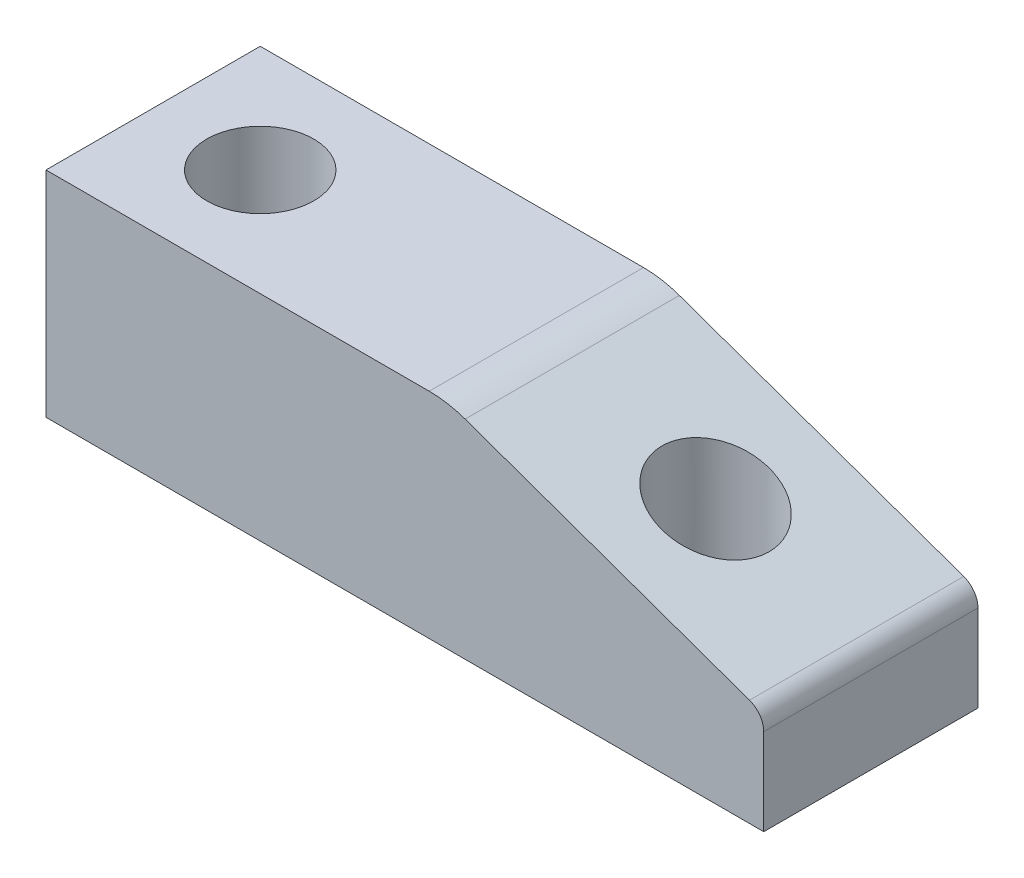
SolidWorks part; units mm, degrees
ref_plane "Front Plane" through (0, 0, 0) normal (0, 0, 1) x (1, 0, 0)
ref_plane "Top Plane" through (0, 0, 0) normal (0, 1, 0) x (1, 0, 0)
ref_plane "Right Plane" through (0, 0, 0) normal (1, 0, 0) x (0, 0, -1)
sketch "Sketch1" plane through (0, 0, 0) normal (0, 0, 1) x (1, 0, 0)
  line L5 (-27.7934, 28.2767) -> (-27.7934, -11.7233)
  line L6 (-27.7934, -11.7233) -> (106.2066, -11.7233)
  line L7 (106.2066, -11.7233) -> (106.2066, 4.4546)
  line L8 (103.5479, 8.223) -> (50.4599, 27.1188)
  line L9 (43.7534, 28.2767) -> (-27.7934, 28.2767)
  arc A0 (43.7534, 28.2767) -> (50.4599, 27.1188) centre (43.7534, 8.2767) cw
  arc A1 (106.2066, 4.4546) -> (103.5479, 8.223) centre (102.2066, 4.4546) ccw
  point P2 (0, 0)
  point P8 (47.2066, 28.2767)
  point P11 (106.2066, 7.2767)
  dimension "D4" = 20
  dimension "D6" = 4
  dimension "D1" = 40
  dimension "D2" = 134
  dimension "D3" = 19
  dimension "D5" = 75
extrude "Boss-Extrude1" add sketch "Sketch1" against normal blind 40
sketch "Sketch2" plane through (0, 28.2767, 0) normal (0, 1, 0) x (1, 0, 0)
  line L0 (43.7534, 0) -> (-27.7934, 0) construction
  line L2 (103.5479, 40) -> (50.4599, 40) construction
  line L3 (-27.7934, 40) -> (-27.7934, 0) construction
  line L4 (106.2066, 40) -> (106.2066, 0) construction
  circle A0 centre (-7.7934, 20) radius 10
  circle A1 centre (-7.7934, 20) radius 6
  circle A2 centre (77.2066, 20) radius 10
  circle A3 centre (77.2066, 20) radius 6
  dimension "D1" = 20
  dimension "D2" = 12
  dimension "D3" = 20
  dimension "D4" = 12
  dimension "D5" = 85
  dimension "D6" = 20
  dimension "D7" = 20
  dimension "D8" = 20
  dimension "D9" = 29
extrude "Cut-Extrude1" cut sketch "Sketch2" against normal up to surface (40 mm away) contours A3 | A1 up to face at (39.2066, -11.7233, -20)
extrude "Cut-Extrude2" cut sketch "Sketch2<3>" against normal blind 29 contours A2 | A0
sketch "Sketch2<3>" plane through (0, 28.2767, 0) normal (0, 1, 0) x (1, 0, 0) same geometry as "Sketch2"
